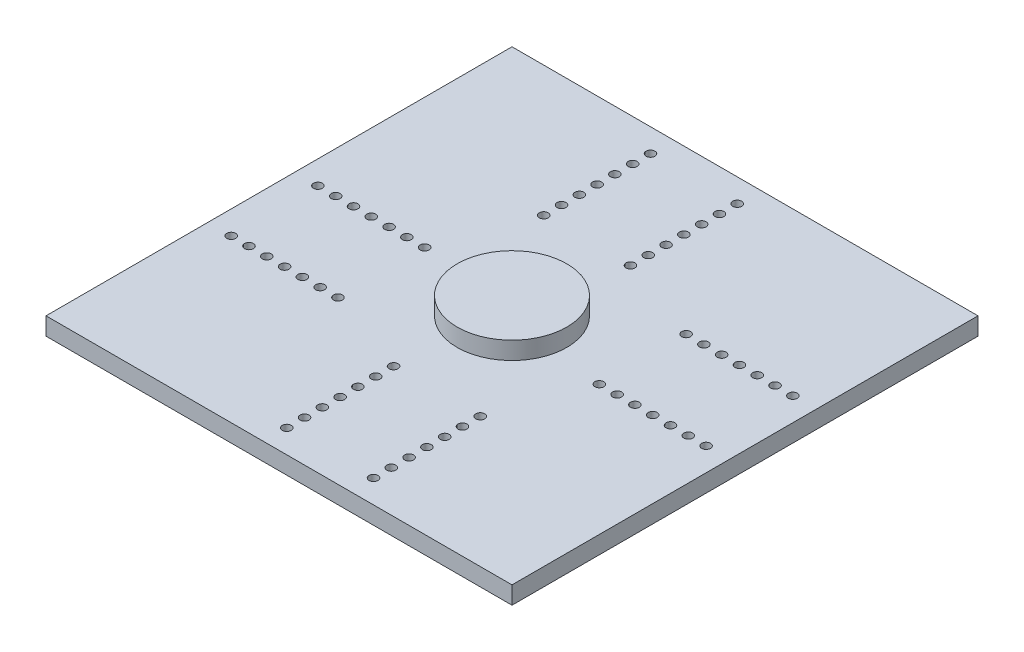
SolidWorks part; units mm, degrees
ref_plane "Front Plane" through (0, 0, 0) normal (0, 0, 1) x (1, 0, 0)
ref_plane "Top Plane" through (0, 0, 0) normal (0, 1, 0) x (1, 0, 0)
ref_plane "Right Plane" through (0, 0, 0) normal (1, 0, 0) x (0, 0, -1)
sketch "Sketch1" plane through (0, 0, 0) normal (0, 1, 0) x (1, 0, 0)
  line L1 (-83.82, 83.82) -> (83.82, 83.82)
  line L2 (-83.82, 83.82) -> (-83.82, -83.82)
  line L3 (-83.82, -83.82) -> (83.82, -83.82)
  line L4 (83.82, 83.82) -> (83.82, -83.82)
  line L5 (-83.82, 83.82) -> (83.82, -83.82) construction
  line L6 (-83.82, -83.82) -> (83.82, 83.82) construction
  point P0 (0, 0)
  dimension "D1" = 167.64
extrude "Boss-Extrude1" add sketch "Sketch1" along normal blind 6.35
sketch "Sketch2" plane through (0, 6.35, 0) normal (0, 1, 0) x (1, 0, 0)
  circle A0 centre (0, 0) radius 19.7258
extrude "Boss-Extrude2" add sketch "Sketch2" along normal blind 6.35
sketch "Sketch3" plane through (0, 6.35, 0) normal (0, 1, 0) x (1, 0, 0)
  line L0 (5.6, 83.82) -> (5.6, -83.82) construction
  line L1 (83.82, 83.82) -> (-83.82, 83.82) construction
  line L2 (-83.82, -83.82) -> (83.82, -83.82) construction
  line L3 (-25.6, 83.82) -> (-25.6, -83.82) construction
  line L4 (5.6, 75.42) -> (-25.6, 75.42) construction
  circle A0 centre (5.6, 75.42) radius 1.6
  circle A1 centre (-25.6, 75.42) radius 1.6
  circle A2 centre (5.6, 69.02) radius 1.6
  circle A3 centre (-25.6, 69.02) radius 1.6
  circle A4 centre (5.6, 62.62) radius 1.6
  circle A5 centre (-25.6, 62.62) radius 1.6
  circle A6 centre (5.6, 56.22) radius 1.6
  circle A7 centre (-25.6, 56.22) radius 1.6
  circle A8 centre (5.6, 49.82) radius 1.6
  circle A9 centre (-25.6, 49.82) radius 1.6
  circle A10 centre (5.6, 43.42) radius 1.6
  circle A11 centre (-25.6, 43.42) radius 1.6
  circle A12 centre (5.6, 37.02) radius 1.6
  circle A13 centre (-25.6, 37.02) radius 1.6
  circle A14 centre (75.42, -5.6) radius 1.6
  circle A15 centre (75.42, 25.6) radius 1.6
  circle A16 centre (69.02, -5.6) radius 1.6
  circle A17 centre (62.62, -5.6) radius 1.6
  circle A18 centre (56.22, -5.6) radius 1.6
  circle A19 centre (49.82, -5.6) radius 1.6
  circle A20 centre (43.42, -5.6) radius 1.6
  circle A21 centre (37.02, -5.6) radius 1.6
  circle A22 centre (69.02, 25.6) radius 1.6
  circle A23 centre (62.62, 25.6) radius 1.6
  circle A24 centre (56.22, 25.6) radius 1.6
  circle A25 centre (49.82, 25.6) radius 1.6
  circle A26 centre (43.42, 25.6) radius 1.6
  circle A27 centre (37.02, 25.6) radius 1.6
  circle A28 centre (-5.6, -75.42) radius 1.6
  circle A29 centre (25.6, -75.42) radius 1.6
  circle A30 centre (-5.6, -69.02) radius 1.6
  circle A31 centre (-5.6, -62.62) radius 1.6
  circle A32 centre (-5.6, -56.22) radius 1.6
  circle A33 centre (-5.6, -49.82) radius 1.6
  circle A34 centre (-5.6, -43.42) radius 1.6
  circle A35 centre (-5.6, -37.02) radius 1.6
  circle A36 centre (25.6, -69.02) radius 1.6
  circle A37 centre (25.6, -62.62) radius 1.6
  circle A38 centre (25.6, -56.22) radius 1.6
  circle A39 centre (25.6, -49.82) radius 1.6
  circle A40 centre (25.6, -43.42) radius 1.6
  circle A41 centre (25.6, -37.02) radius 1.6
  circle A42 centre (-75.42, 5.6) radius 1.6
  circle A43 centre (-75.42, -25.6) radius 1.6
  circle A44 centre (-69.02, 5.6) radius 1.6
  circle A45 centre (-62.62, 5.6) radius 1.6
  circle A46 centre (-56.22, 5.6) radius 1.6
  circle A47 centre (-49.82, 5.6) radius 1.6
  circle A48 centre (-43.42, 5.6) radius 1.6
  circle A49 centre (-37.02, 5.6) radius 1.6
  circle A50 centre (-69.02, -25.6) radius 1.6
  circle A51 centre (-62.62, -25.6) radius 1.6
  circle A52 centre (-56.22, -25.6) radius 1.6
  circle A53 centre (-49.82, -25.6) radius 1.6
  circle A54 centre (-43.42, -25.6) radius 1.6
  circle A55 centre (-37.02, -25.6) radius 1.6
  point P124 (0, 0)
  dimension "D4" = 3.2
  dimension "D1" = 5.6
  dimension "D2" = 8.4
  dimension "D3" = 31.2
  dimension "D5" = 7
  dimension "D6" = 4
extrude "Cut-Extrude1" cut sketch "Sketch3" against normal blind 10
